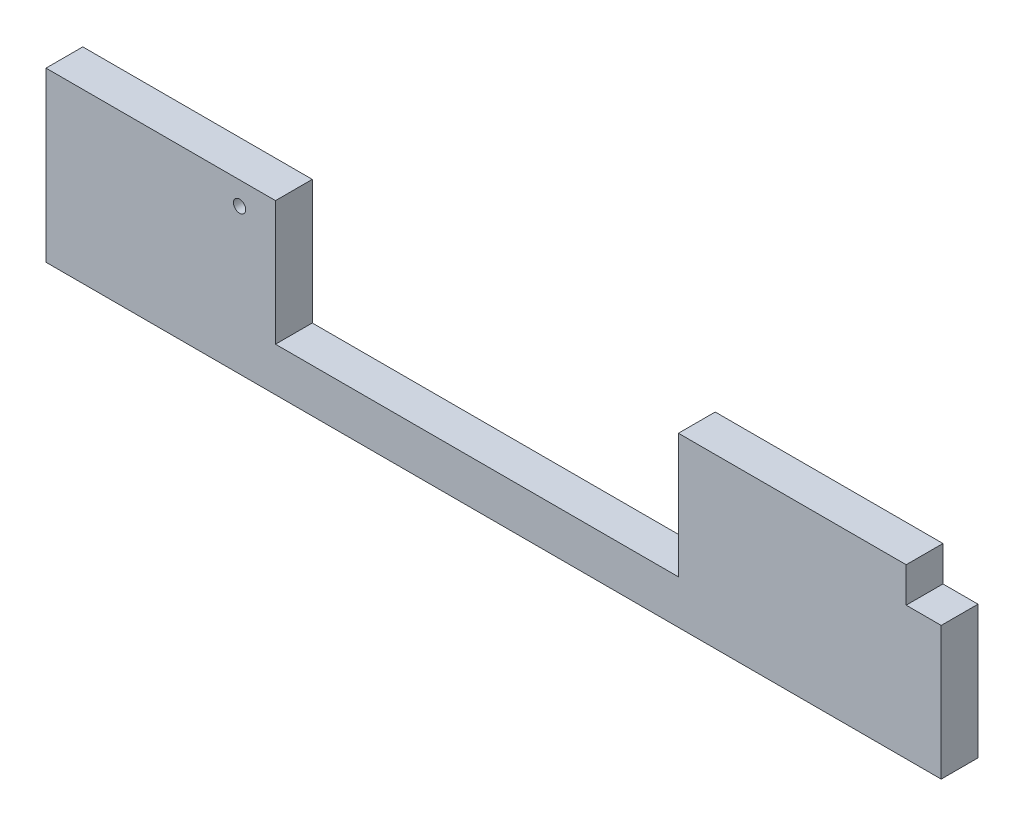
SolidWorks part; units mm, degrees
ref_plane "Front Plane" through (0, 0, 0) normal (0, 0, 1) x (1, 0, 0)
ref_plane "Top Plane" through (0, 0, 0) normal (0, 1, 0) x (1, 0, 0)
ref_plane "Right Plane" through (0, 0, 0) normal (1, 0, 0) x (0, 0, -1)
sketch "Sketch1" plane through (0, 0, 0) normal (0, 0, 1) x (1, 0, 0)
  line L1 (-85.0624, -35.0708) -> (44.7316, -35.0708)
  line L2 (-85.0624, -35.0708) -> (-85.0624, -59.4548)
  line L3 (-85.0624, -59.4548) -> (44.7316, -59.4548)
  line L4 (44.7316, -35.0708) -> (44.7316, -59.4548)
  dimension "D1" = 129.794
  dimension "D2" = 24.384
extrude "Boss-Extrude1" add sketch "Sketch1" along normal blind 5.334
sketch "Sketch3" plane through (0, 0, 5.334) normal (0, 0, 1) x (1, 0, 0)
  line L0 (44.7316, -35.0708) -> (-85.0624, -35.0708) construction
  line L1 (-51.7884, -35.0708) -> (6.6316, -35.0708)
  line L2 (-51.7884, -35.0708) -> (-51.7884, -53.1048)
  line L3 (-51.7884, -53.1048) -> (6.6316, -53.1048)
  line L4 (6.6316, -35.0708) -> (6.6316, -53.1048)
  line L5 (44.7316, -59.4548) -> (44.7316, -35.0708) construction
  dimension "D1" = 38.1
  dimension "D2" = 58.42
  dimension "D3" = 18.034
extrude "Cut-Extrude1" cut sketch "Sketch3" against normal through all
sketch "Sketch4" plane through (0, 0, 5.334) normal (0, 0, 1) x (1, 0, 0)
  line L1 (-85.0624, -47.2628) -> (-69.9279, -47.2628) construction
  line L2 (-85.0624, -35.0708) -> (-85.0624, -59.4548) construction
  line L3 (-68.4254, -35.0708) -> (-68.4254, -42.5901) construction
  circle A0 centre (-56.9954, -38.3728) radius 0.889
  dimension "D1" = 1.778
  dimension "D2" = 8.89
  dimension "D3" = 11.43
extrude "Cut-Extrude2" cut sketch "Sketch4" against normal through all
sketch "Sketch5" plane through (0, 0, 5.334) normal (0, 0, 1) x (1, 0, 0)
  line L1 (39.6516, -40.1508) -> (47.0415, -40.1508)
  line L2 (39.6516, -40.1508) -> (39.6516, -30.6562)
  line L3 (39.6516, -30.6562) -> (47.0415, -30.6562)
  line L4 (47.0415, -40.1508) -> (47.0415, -30.6562)
  line L5 (44.7316, -59.4548) -> (44.7316, -35.0708) construction
  line L6 (44.7316, -35.0708) -> (6.6316, -35.0708) construction
  dimension "D1" = 5.08
  dimension "D2" = 5.08
extrude "Cut-Extrude3" cut sketch "Sketch5" against normal through all
equation "\"MDF\"= .21in"
equation "\"Foamcore\"= .13in"
equation "\"Gmaterial\"= \"MDF\""
equation "\"D2@Sketch1\"=\"MDF\"+.25+.5"
equation "\"D1@Boss-Extrude1\"=\"MDF\""
equation "\"D3@Sketch3\"=\"MDF\"+.5"
